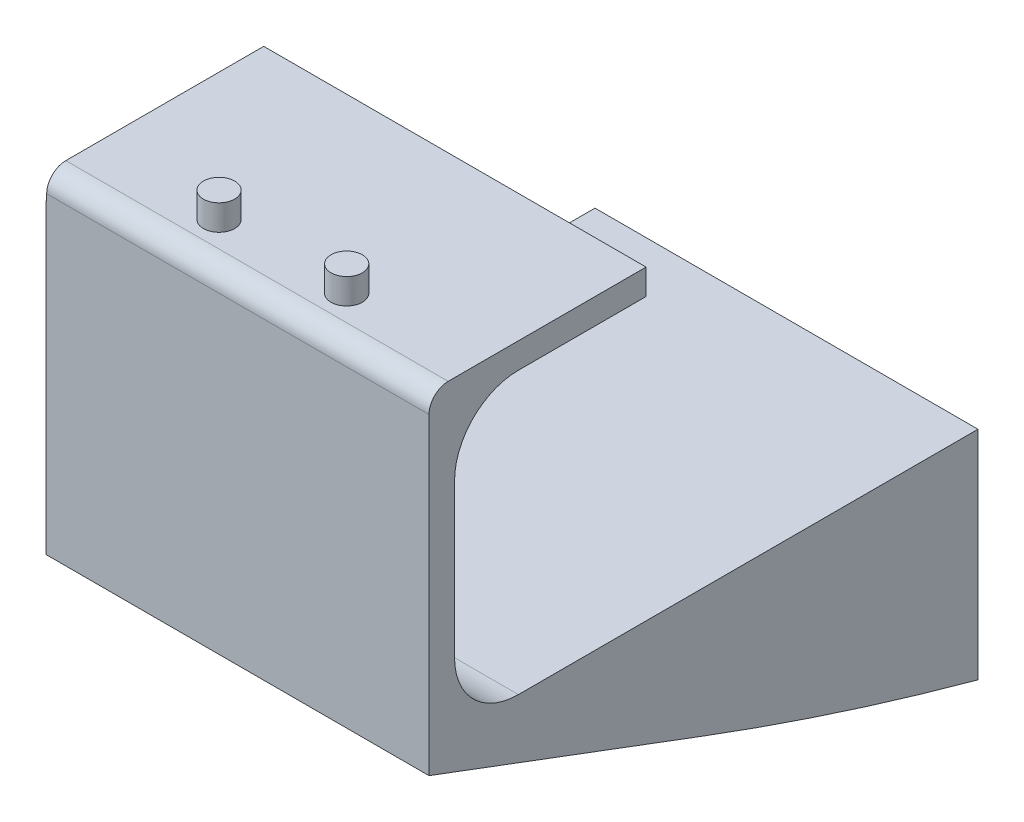
SolidWorks part; units mm, degrees
ref_plane "Front Plane" through (0, 0, 0) normal (0, 0, 1) x (1, 0, 0)
ref_plane "Top Plane" through (0, 0, 0) normal (0, 1, 0) x (1, 0, 0)
ref_plane "Right Plane" through (0, 0, 0) normal (1, 0, 0) x (0, 0, -1)
ref_plane "Plane1" through (18, 0, 0) normal (-1, 0, 0) x (0, -1, 0)
sketch "Sketch1" plane through (18, 0, 0) normal (-1, 0, 0) x (0, -1, 0)
  line L0 (-0.8382, 3) -> (-0.8382, 0)
  line L1 (-0.8382, 0) -> (0, 0)
  arc A0 (0, 0) -> (-0.8382, 3) centre (-236.8592, -64.5597) ccw
extrude "Boss-Extrude1" add sketch "Sketch1" against normal blind 24
sketch "Sketch2" plane through (0, 0.8382, 0) normal (0, 1, 0) x (-1, 0, 0)
  line L0 (-42, 21.6411) -> (-18, 21.6411)
  line L1 (-18, 21.6411) -> (-18, 0)
  line L2 (-18, 0) -> (-42, 0)
  line L3 (-42, 0) -> (-42, 21.6411)
extrude "Boss-Extrude2" add sketch "Sketch2" along normal blind 14.1618
sketch "Sketch3" plane through (42, 0, 0) normal (1, 0, 0) x (0, 0, -1)
  line L0 (0, 15) -> (0, 0)
  line L1 (-21.6411, 6.9904) -> (-43, 15)
  line L2 (-43, 15) -> (0, 15)
  arc A0 (0, 0) -> (-21.6411, 6.9904) centre (64.5597, 236.8592) cw
extrude "Boss-Extrude3" add sketch "Sketch3" along normal blind 3
sketch "Sketch4" plane through (0, 0, 21.6411) normal (0, 0, 1) x (1, 0, 0)
  line L0 (42, 15) -> (42, 6.9904)
  line L1 (42, 6.9904) -> (42, 0.8382)
  line L2 (42, 0.8382) -> (18, 0.8382)
  line L3 (18, 0.8382) -> (18, 6.9904)
  line L4 (18, 6.9904) -> (18, 15)
  line L5 (18, 15) -> (42, 15)
extrude "Boss-Extrude4" add sketch "Sketch4" along normal blind 21.3589
sketch "Sketch5" plane through (0, 15, 0) normal (0, 1, 0) x (-1, 0, 0)
  line L0 (-18, 0) -> (-45, 0)
  line L1 (-45, 0) -> (-45, 43)
  line L2 (-45, 43) -> (-18, 43)
  line L3 (-18, 43) -> (-18, 0)
extrude "Boss-Extrude5" add sketch "Sketch5" along normal blind 24
sketch "Sketch6" plane through (0, 0.8382, 0) normal (0, -1, 0) x (1, 0, 0)
  line L0 (18, 3) -> (42, 3)
  line L1 (42, 3) -> (42, 21.6411)
  line L2 (42, 21.6411) -> (42, 43)
  line L3 (42, 43) -> (18, 43)
  line L4 (18, 43) -> (18, 3)
extrude "Cut-Extrude1" cut sketch "Sketch6" against normal blind 6.1522
sketch "Sketch7" plane through (0, 6.9904, 0) normal (0, -1, 0) x (1, 0, 0)
  line L0 (18, 3) -> (42, 3)
  line L1 (42, 3) -> (42, 43)
  line L2 (42, 43) -> (18, 43)
  line L3 (18, 43) -> (18, 3)
extrude "Cut-Extrude2" cut sketch "Sketch7" against normal blind 8.0096
sketch "Sketch8" plane through (18, 0, 0) normal (-1, 0, 0) x (0, 0, 1)
  line L0 (0, 39) -> (43, 39)
  line L1 (43, 39) -> (43, 15)
  line L2 (43, 15) -> (21.6411, 6.9904)
  line L3 (0, 0) -> (0, 39)
  arc A0 (21.6411, 6.9904) -> (0, 0) centre (-64.5597, 236.8592) cw
extrude "Boss-Extrude6" add sketch "Sketch8" along normal blind 3
sketch "Sketch9" plane through (15, 0, 0) normal (-1, 0, 0) x (0, 0, 1)
  line L0 (0, 17) -> (41, 17)
  line L1 (41, 17) -> (41, 39)
  line L2 (41, 39) -> (0, 39)
  line L3 (0, 39) -> (0, 17)
extrude "Cut-Extrude3" cut sketch "Sketch9" against normal through all
sketch "Sketch10" plane through (0, 39, 0) normal (0, 1, 0) x (-1, 0, 0)
  line L0 (-15.053, 26) -> (-45, 26)
  line L1 (-45, 26) -> (-45, 43)
  line L2 (-45, 43) -> (-15.053, 43)
  line L3 (-15.053, 43) -> (-15.053, 26)
extrude "Boss-Extrude7" add sketch "Sketch10" along normal blind 2
ref_plane "Plane2" through (0, 0, 36) normal (0, 0, -1) x (-1, 0, 0)
sketch "Sketch11" plane through (0, 0, 36) normal (0, 0, -1) x (-1, 0, 0)
  line L0 (-26.225, 41) -> (-25, 41)
  line L1 (-25, 41) -> (-25, 43)
  line L2 (-25, 43) -> (-26.225, 43)
  line L3 (-26.225, 43) -> (-26.225, 41)
  line L4 (-25, 41) -> (-25, 43) construction
sketch "Sketch12" plane through (0, 0, 36) normal (0, 0, -1) x (-1, 0, 0)
  line L0 (-36.225, 41) -> (-35, 41)
  line L1 (-35, 41) -> (-35, 43)
  line L2 (-35, 43) -> (-36.225, 43)
  line L3 (-36.225, 43) -> (-36.225, 41)
  line L4 (-35, 41) -> (-35, 43) construction
hole_wizard "Ø5.0 (5) Diameter Hole1" positions "Sketch14" profile "Sketch13" hole size "Ø5.0" standard "ANSI Metric"
sketch "Sketch14" plane through (0, 0, 3) normal (0, 0, 1) x (1, 0, 0)
  point P0 (36, 10)
  point P1 (24, 10)
sketch "Sketch13" plane through (36, 10, 3) normal (1, 0, 0) x (0, -1, 0)
  line L0 (0, 0) -> (0, 3)
  line L1 (0, 3) -> (2.5, 3)
  line L2 (2.5, 3) -> (2.5, 0)
  line L5 (2.5, 0) -> (0, 0)
  line L11 (0, -6.35) -> (0, 107.95) construction
  dimension "Thru Hole Dia." = 5
  dimension "Thru Hole Depth" = 3
fillet "Fillet1" radius 1.5 1 edges at (30.0265, 41, 43) tangent propagation no
fillet "Fillet2" radius 5 2 edges at (30, 17, 41) (30.0265, 39, 41) tangent propagation no
sketch "Sketch15" plane through (0, 41, 0) normal (0, 1, 0) x (1, 0, 0)
  line L0 (15.053, -26) -> (15.053, -41.5) construction
  line L4 (15.053, -41.5) -> (45, -41.5) construction
  circle A0 centre (25.053, -39.5) radius 1.225
  circle A1 centre (35.053, -39.5) radius 1.225
  point P8 (27.8688, -41.5)
  point P9 (32.1313, -36.2394)
  dimension "D1" = 10
  dimension "D2" = 10
  dimension "D3" = 2
  dimension "D4" = 2
extrude "Boss-Extrude8" add sketch "Sketch15" along normal blind 2
